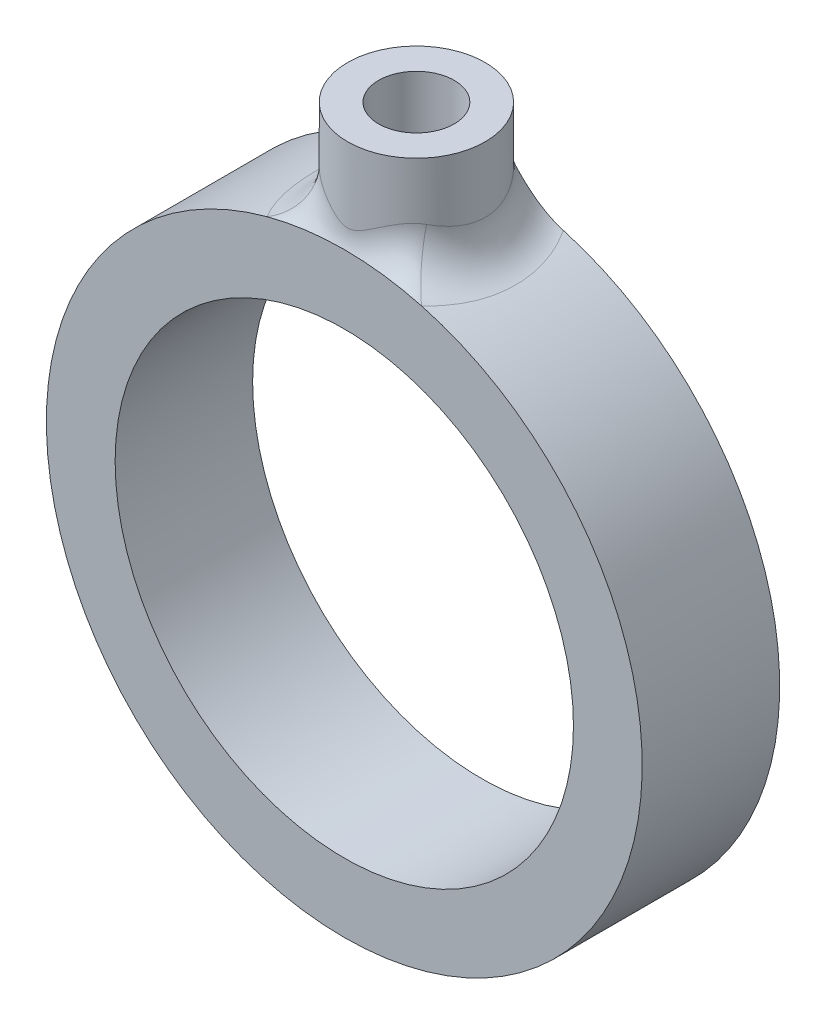
SolidWorks part; units mm, degrees
ref_plane "Front Plane" through (0, 0, 0) normal (0, 0, 1) x (1, 0, 0)
ref_plane "Top Plane" through (0, 0, 0) normal (0, 1, 0) x (1, 0, 0)
ref_plane "Right Plane" through (0, 0, 0) normal (1, 0, 0) x (0, 0, -1)
sketch "Sketch4" plane through (0, 0, 0) normal (0, 0, 1) x (1, 0, 0)
  circle A0 centre (0, 0) radius 10
  circle A1 centre (0, 0) radius 13
extrude "Boss-Extrude3" add sketch "Sketch4" along normal blind 6
sketch "Sketch6" plane through (0, 0, 0) normal (0, 1, 0) x (1, 0, 0)
  circle A0 centre (0.0034, -2.8563) radius 3
extrude "Boss-Extrude14" add sketch "Sketch6" against normal blind 5 from offset 17
fillet "Fillet3" radius 2 1 edges at (0.4352, 12.9927, 5.825)
hole_wizard "M4 Tapped Hole1" positions "3DSketch1" profile "Sketch7" tap size "M4" standard "ISO"
sketch3d "3DSketch1"
  line L0 (0.0034, 12, 2.8563) -> (0.0034, 17, 2.8563) construction
  point P0 (0.0034, 17, 2.8563)
  point P4 (0.0034, 17, 2.8563)
  point P6 (0.0034, 17, 2.8563)
sketch "Sketch7" plane through (0.0034, 17, 2.8563) normal (1, 0, 0) x (0, 0, 1)
  line L0 (0, 0) -> (0, 13.7914)
  line L1 (0, 13.7914) -> (1.65, 12.8)
  line L2 (1.65, 12.8) -> (1.65, 0)
  line L5 (1.65, 0) -> (0, 0)
  line L10 (0, 13.7914) -> (-1.65, 12.8) construction
  line L11 (0, -6.35) -> (0, 107.95) construction
  dimension "Tap Drill Dia." = 3.3
  dimension "Tap Drill Depth" = 12.8
  dimension "Drill Angle" = 118
cosmetic thread "Hole Thread1" parameters "D1"=8, "D2"=4
cosmetic thread "Hole Thread2" parameters "D1"=8, "D2"=4
cosmetic thread "Hole Thread3" parameters "D1"=8, "D2"=4
